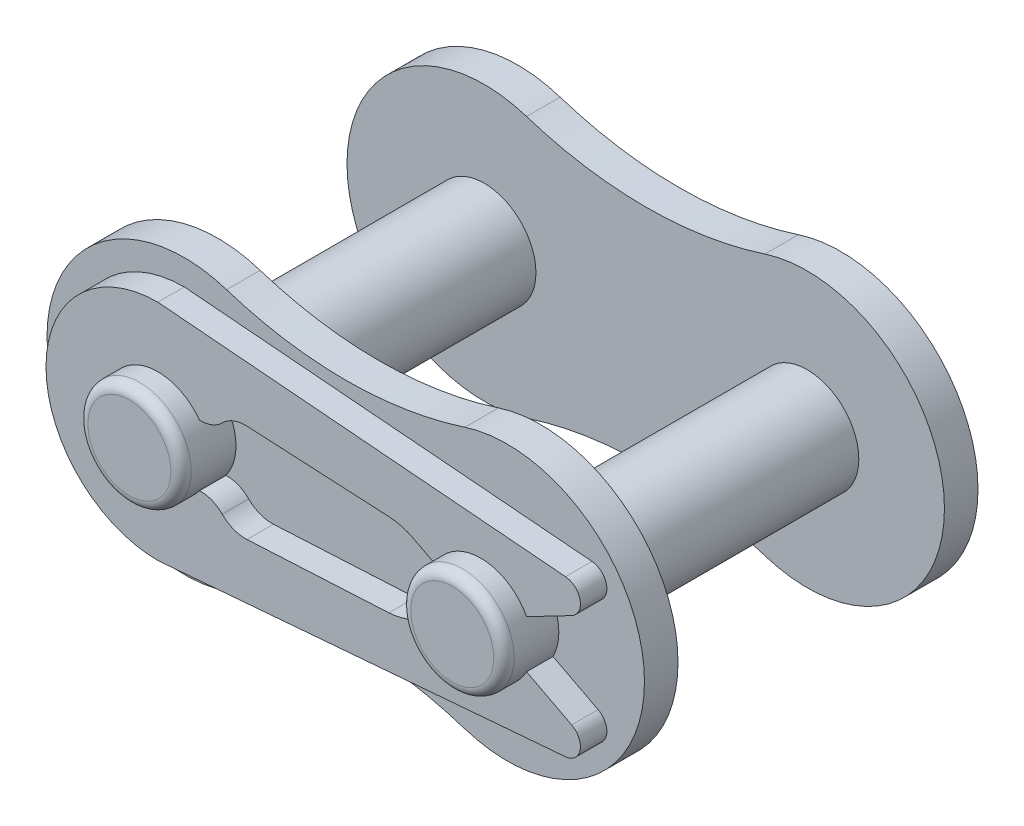
SolidWorks part; units mm, degrees
ref_plane "Front Plane" through (0, 0, 0) normal (0, 0, 1) x (1, 0, 0)
ref_plane "Top Plane" through (0, 0, 0) normal (0, 1, 0) x (1, 0, 0)
ref_plane "Right Plane" through (0, 0, 0) normal (1, 0, 0) x (0, 0, -1)
ref_axis "Axis_X" through (-24.0938, 0, 0) along (1, 0, 0)
ref_axis "Axis_Y" through (0, 7.425, 0) along (0, -1, 0)
ref_axis "Axis_Z" through (0, 0, -10.625) along (0, 0, 1)
sketch "Sketch1" plane through (0, 0, 0) normal (0, 1, 0) x (1, 0, 0)
  line L0 (0, 0) -> (0, 9.6) construction
  line L1 (0, -10.9) -> (0, 9.6)
  line L2 (4.1, 8.2) -> (2.54, 8.2)
  line L3 (2.54, 8.2) -> (2.54, -10.4)
  line L4 (2.04, -10.9) -> (0, -10.9)
  arc A0 (4.1, 8.2) -> (0, 9.6) centre (0, 2.8964) ccw
  arc A1 (2.04, -10.9) -> (2.54, -10.4) centre (2.04, -10.4) ccw
  dimension "FIX_6" = 0.5
  dimension "FIX_3" = 5.08
  dimension "FIX_4" = 8.2
  dimension "FIX_1" = 9.6
  dimension "FIX_2" = 10.9
  dimension "FIX_5" = 1.4
revolve "Revolve1" add sketch "Sketch1" angle 360 about axis through (0, 0, -10.625) along (0, 0, 1)
sketch "Sketch2" plane through (0, 0, 0) normal (0, -1, 0) x (1, 0, 0)
  line L0 (-15.875, 10.9) -> (-15.875, -9.6) construction
  line L1 (-15.875, 10.9) -> (-17.915, 10.9)
  line L2 (-18.415, 10.4) -> (-18.415, -8.2)
  line L3 (-18.415, -8.2) -> (-19.975, -8.2)
  line L4 (-15.875, -9.6) -> (-15.875, 10.9)
  arc A0 (-19.975, -8.2) -> (-15.875, -9.6) centre (-15.875, -2.8964) ccw
  arc A1 (-18.415, 10.4) -> (-17.915, 10.9) centre (-17.915, 10.4) cw
  dimension "FIX_13" = 0.5
  dimension "FIX_8" = 5.08
  dimension "FIX_9" = 8.2
  dimension "FIX_10" = 1.4
  dimension "FIX_11" = 10.9
  dimension "FIX_12" = 9.6
  dimension "FIX_14" = 15.875
revolve "Revolve2" add sketch "Sketch2" angle 360 about L0
sketch "Sketch3" plane through (0, 0, -8.2) normal (0, 0, 1) x (0, 1, 0)
  line L0 (0, 0) -> (0, 15.875) construction
  line L1 (-6.75, 0) -> (6.75, 0) construction
  arc A0 (-6.4213, 2.0807) -> (6.4213, 2.0807) centre (0, 0) ccw
  arc A1 (6.4213, 13.7943) -> (-6.4213, 13.7943) centre (0, 15.875) ccw
  circle A2 centre (0, 0) radius 2.54
  circle A3 centre (0, 15.875) radius 2.54
  arc A4 (6.4213, 13.7943) -> (6.4213, 2.0807) centre (24.4961, 7.9375) ccw
  arc A5 (-6.4213, 13.7943) -> (-6.4213, 2.0807) centre (-24.4961, 7.9375) cw
  dimension "FIX_16" = 5.08
  dimension "FIX_17" = 19
  dimension "FIX_18" = 13.5
extrude "Boss-Extrude1" add sketch "Sketch3" along normal blind 1.65
mirror "Mirror1" about plane through (0, 0, 0) normal (0, 0, 1) of "Boss-Extrude1"
sketch "Sketch4" plane through (0, 0, 8.2) normal (0, 0, 1) x (1, 0, 0)
  line L0 (0, 0) -> (-15.875, 0) construction
  line L1 (-15.875, 5.5) -> (4.1683, 3.8345)
  line L2 (-15.875, -5.5) -> (4.1683, -3.8345)
  line L3 (0, 0) -> (2.253, 1.1728) construction
  line L4 (0, 0) -> (2.253, -1.1728) construction
  line L5 (2.253, 1.1728) -> (4.4714, 2.3277)
  line L6 (2.253, -1.1728) -> (4.4714, -2.3277)
  line L7 (-3.2917, 1.7136) -> (-2.253, 1.1728)
  line L8 (-4.52, 2.0484) -> (-11.4913, 2.4138)
  line L9 (-3.2917, -1.7136) -> (-2.253, -1.1728)
  line L10 (-4.52, -2.0484) -> (-11.4913, -2.4138)
  arc A0 (-13.8259, 1.5009) -> (-13.8259, -1.5009) centre (-15.875, 0) ccw
  arc A1 (-2.253, -1.1728) -> (-2.253, 1.1728) centre (0, 0) ccw
  arc A2 (-15.875, 5.5) -> (-15.875, -5.5) centre (-15.875, 0) ccw
  arc A3 (4.4714, 2.3277) -> (4.1683, 3.8345) centre (4.102, 3.0373) ccw
  arc A4 (4.1683, -3.8345) -> (4.4714, -2.3277) centre (4.102, -3.0373) ccw
  arc A5 (-3.2917, 1.7136) -> (-4.52, 2.0484) centre (-4.677, -0.9475) ccw
  arc A6 (-11.4913, 2.4138) -> (-12.7105, 1.9432) centre (-11.575, 0.816) ccw
  arc A7 (-13.8259, 1.5009) -> (-12.7105, 1.9432) centre (-13.775, 3) ccw
  arc A10 (-3.2917, -1.7136) -> (-4.52, -2.0484) centre (-4.677, 0.9475) cw
  arc A11 (-11.4913, -2.4138) -> (-12.7105, -1.9432) centre (-11.575, -0.816) cw
  arc A12 (-13.8259, -1.5009) -> (-12.7105, -1.9432) centre (-13.775, -3) cw
  circle M1 centre (0, 0) radius 2.54
  arc M2 (-2.0807, 6.4213) -> (-13.7943, 6.4213) centre (-7.9375, 24.4961) cw
  arc M3 (-13.7943, 6.4213) -> (-13.7943, -6.4213) centre (-15.875, 0) ccw
  arc M4 (-13.7943, -6.4213) -> (-2.0807, -6.4213) centre (-7.9375, -24.4961) cw
  arc M5 (-2.0807, -6.4213) -> (-2.0807, 6.4213) centre (0, 0) ccw
  circle M6 centre (-15.875, 0) radius 2.54
  dimension "FIX_20" = 5.08
  dimension "FIX_21" = 55
  dimension "FIX_22" = 5.5
  dimension "FIX_24" = 0.8
  dimension "FIX_25" = 3
  dimension "FIX_30" = 1.5
  dimension "FIX_31" = 1.6
  dimension "FIX_23" = 9.5
  dimension "FIX_26" = 3
  dimension "FIX_27" = 3
  dimension "FIX_28" = 2.1
  dimension "FIX_29" = 4.3
extrude "Boss-Extrude2" add sketch "Sketch4" along normal blind 1.3 contours M3 M2 M5 | M3 M5 M4 | A12 A7 A6 L8 A5 L7 L5 A3 L1 A2 L2 A4 L6 L9 A10 L10 A11 M6 M1 region at (-5.877, 4.3834, 8.2)
equation "\"Factor\"= 1.082532"
